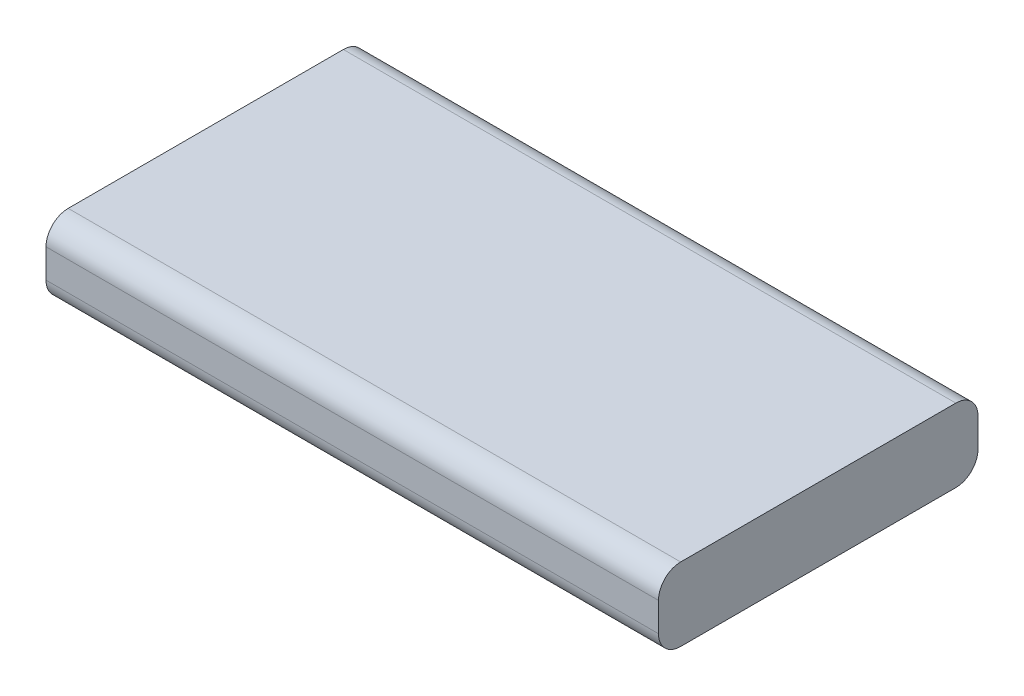
SolidWorks part; units mm, degrees
ref_plane "Front Plane" through (0, 0, 0) normal (0, 0, 1) x (1, 0, 0)
ref_plane "Top Plane" through (0, 0, 0) normal (0, 1, 0) x (1, 0, 0)
ref_plane "Right Plane" through (0, 0, 0) normal (1, 0, 0) x (0, 0, -1)
sketch "Sketch1" plane through (0, 0, 0) normal (0, 1, 0) x (1, 0, 0)
  line L1 (-13.8, 7.2) -> (13.8, 7.2)
  line L2 (-13.8, 7.2) -> (-13.8, -7.2)
  line L3 (-13.8, -7.2) -> (13.8, -7.2)
  line L4 (13.8, 7.2) -> (13.8, -7.2)
  line L5 (-13.8, 7.2) -> (13.8, -7.2) construction
  line L6 (-13.8, -7.2) -> (13.8, 7.2) construction
  point P0 (0, 0)
  dimension "D1" = 27.6
  dimension "D2" = 14.4
extrude "Boss-Extrude1" add sketch "Sketch1" along normal blind 1.65 and the other way blind 1.65
fillet "Fillet1" radius 1 4 edges at (0, -1.65, -7.2) (0, 1.65, -7.2) (0, -1.65, 7.2) (0, 1.65, 7.2)
